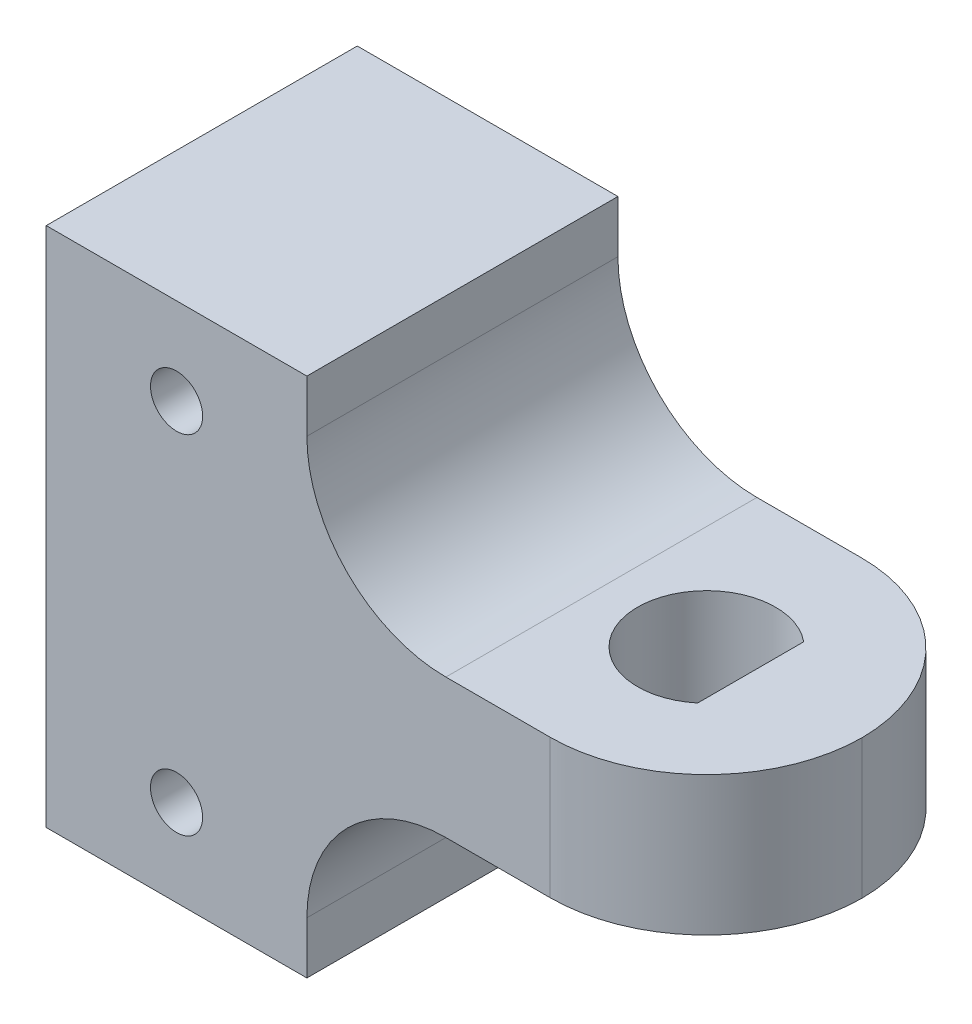
SolidWorks part; units mm, degrees
ref_plane "Front" through (0, 0, 0) normal (0, 0, 1) x (1, 0, 0)
ref_plane "Top" through (0, 0, 0) normal (0, 1, 0) x (1, 0, 0)
ref_plane "Right" through (0, 0, 0) normal (1, 0, 0) x (0, 0, -1)
sketch "Esquisse1" plane through (0, 0, 0) normal (0, 0, 1) x (1, 0, 0)
  line L0 (7.5, 4) -> (30.5, 4)
  line L1 (-7.5, 15) -> (7.5, 15)
  line L2 (-7.5, 15) -> (-7.5, -15)
  line L3 (-7.5, -15) -> (7.5, -15)
  line L4 (7.5, 15) -> (7.5, 4)
  line L5 (-7.5, 15) -> (7.5, -15) construction
  line L6 (-7.5, -15) -> (7.5, 15) construction
  line L7 (30.5, 4) -> (30.5, -4)
  line L8 (30.5, -4) -> (7.5, -4)
  line L9 (7.5, -4) -> (7.5, -15)
  point P0 (0, 0)
  dimension "D1" = 8
  dimension "D2" = 30
  dimension "D3" = 15
  dimension "D4" = 23
extrude "Boss.-Extru.1" add sketch "Esquisse1" along normal blind 17.9
fillet "Congé1" radius 9 2 edges at (30.5, 0, 0) (30.5, 0, 17.9)
sketch "Esquisse2" plane through (0, 4, 0) normal (0, 1, 0) x (1, 0, 0)
  line L0 (24.04, -5.8489) -> (24.04, -11.9511)
  line L1 (7.5, -17.9) -> (7.5, 0) construction
  arc A0 (24.04, -5.8489) -> (24.04, -11.9511) centre (21.5, -8.9) ccw
  dimension "D2" = 3.97
  dimension "D1" = 2.54
extrude "Enlèv. mat.-Extru.1" cut sketch "Esquisse2" against normal up to next
sketch "Esquisse3" plane through (0, 0, 17.9) normal (0, 0, 1) x (1, 0, 0)
  line L0 (7.5, 15) -> (-7.5, 15) construction
  line L1 (50, 0) -> (-50, 0) construction
  line L2 (-7.5, 15) -> (-7.5, -15) construction
  circle A0 centre (0, 10) radius 1.5
  circle A1 centre (0, -10) radius 1.5
  dimension "D1" = 5
  dimension "D2" = 3
  dimension "D3" = 7.5
extrude "Enlèv. mat.-Extru.2" cut sketch "Esquisse3" against normal up to next
fillet "Congé2" radius 8 2 edges at (7.5, -4, 8.95) (7.5, 4, 8.95)
